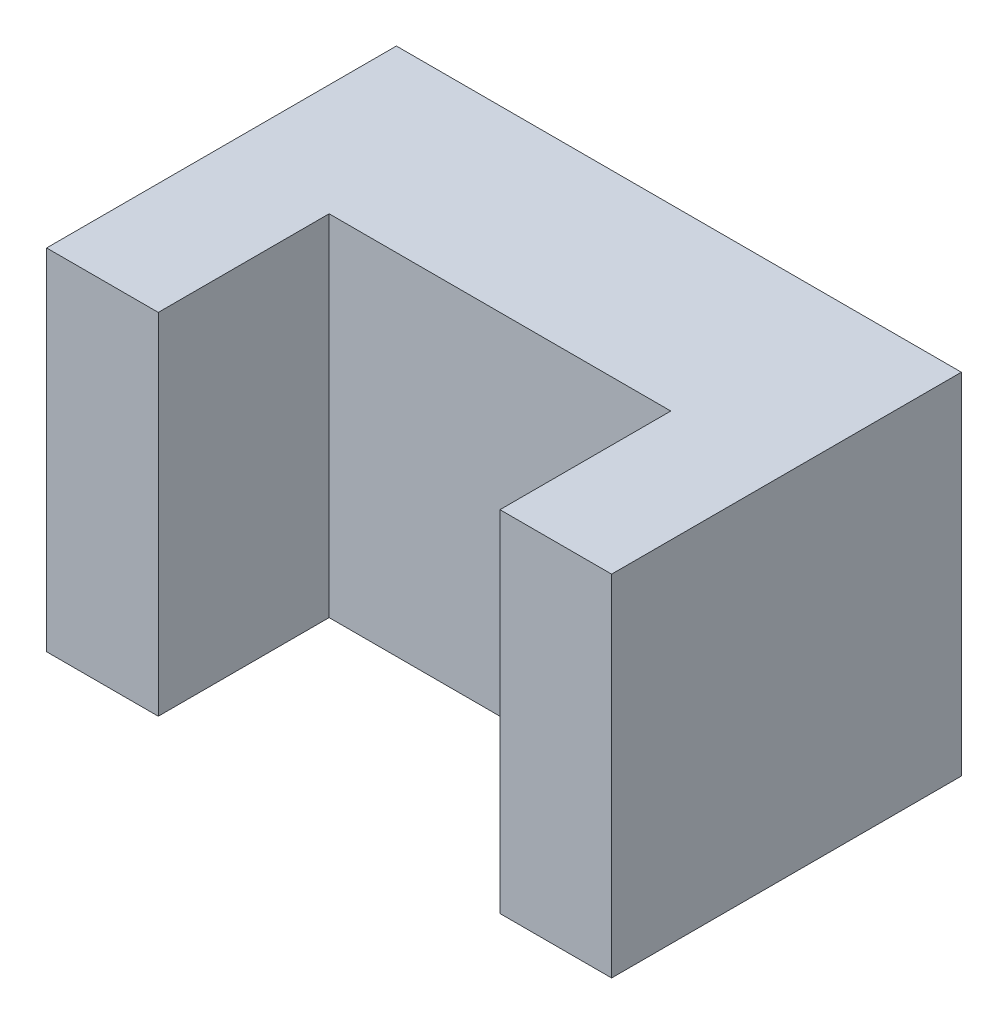
SolidWorks part; units mm, degrees
ref_plane "Plan de face" through (0, 0, 0) normal (0, 0, 1) x (1, 0, 0)
ref_plane "Plan de dessus" through (0, 0, 0) normal (0, 1, 0) x (1, 0, 0)
ref_plane "Plan de droite" through (0, 0, 0) normal (1, 0, 0) x (0, 0, -1)
sketch "Esquisse1" plane through (0, 0, 0) normal (0, 1, 0) x (1, 0, 0)
  line L1 (-21, 13) -> (21, 13)
  line L2 (-21, 13) -> (-21, -13)
  line L3 (-21, -13) -> (21, -13)
  line L4 (21, 13) -> (21, -13)
  point P4 (0, 13)
  point P6 (21, 0)
  dimension "D1" = 26
  dimension "D2" = 42
extrude "Boss.-Extru.1" add sketch "Esquisse1" along normal blind 26
sketch "Esquisse2" plane through (0, 26, 0) normal (0, 1, 0) x (1, 0, 0)
  line L0 (-21, -13) -> (21, -13) construction
  line L1 (-12.7, -0.3) -> (12.7, -0.3)
  line L2 (-12.7, -0.3) -> (-12.7, -13)
  line L3 (-12.7, -13) -> (12.7, -13)
  line L4 (12.7, -0.3) -> (12.7, -13)
  point P6 (0, -0.3)
  dimension "D1" = 12.7
  dimension "D2" = 25.4
extrude "Enlèv. mat.-Extru.1" cut sketch "Esquisse2" against normal blind 26
